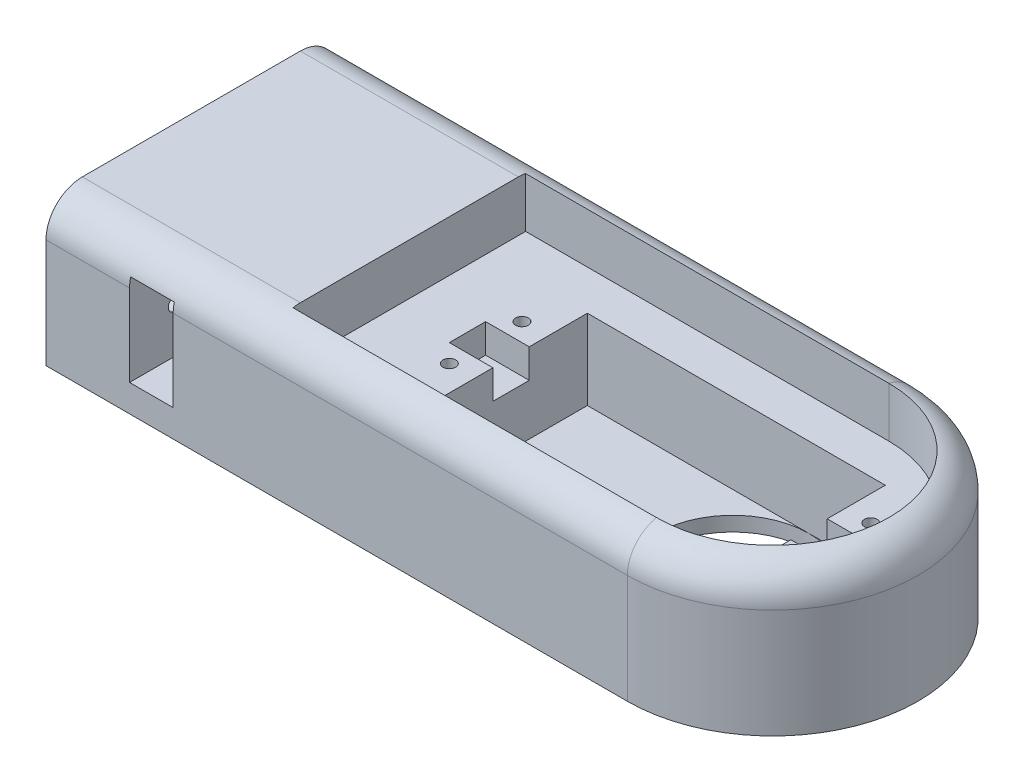
SolidWorks part; units mm, degrees
ref_plane "Front Plane" through (0, 0, 0) normal (0, 0, 1) x (1, 0, 0)
ref_plane "Top Plane" through (0, 0, 0) normal (0, 1, 0) x (1, 0, 0)
ref_plane "Right Plane" through (0, 0, 0) normal (1, 0, 0) x (0, 0, -1)
sketch "Sketch1" plane through (0, 0, 0) normal (0, 1, 0) x (1, 0, 0)
  line L0 (0, 40) -> (0, 0)
  line L1 (0, 0) -> (80, 0)
  line L3 (80, 40) -> (0, 40)
  arc A0 (80, 0) -> (80, 40) centre (80, 20) ccw
  dimension "D1" = 40
  dimension "D2" = 80
extrude "Boss-Extrude1" add sketch "Sketch1" along normal blind 20 contours L1 A0 L3 L0
sketch "Sketch2" plane through (0, 20, 0) normal (0, 1, 0) x (1, 0, 0)
  line L0 (80, 40) -> (80, 0) construction
  line L1 (80, 40) -> (0, 40) construction
  line L2 (85, 30.5) -> (44, 30.5)
  line L3 (85, 30.5) -> (85, 9.5)
  line L4 (85, 9.5) -> (44, 9.5)
  line L5 (44, 30.5) -> (44, 9.5)
  line L6 (85, 30.5) -> (44, 9.5) construction
  line L7 (85, 9.5) -> (44, 30.5) construction
  line L8 (88.5, 25) -> (40.5, 25)
  line L9 (88.5, 25) -> (88.5, 15)
  line L10 (88.5, 15) -> (40.5, 15)
  line L11 (40.5, 25) -> (40.5, 15)
  line L12 (88.5, 25) -> (40.5, 15) construction
  line L13 (88.5, 15) -> (40.5, 25) construction
  line L16 (30, 40) -> (30, 0)
  line L17 (30, 36) -> (30, 4)
  line L20 (0, 4) -> (80, 4)
  line L21 (80, 36) -> (0, 36)
  line L22 (30, 4) -> (80, 4)
  line L23 (80, 36) -> (30, 36)
  arc A0 (80, 0) -> (80, 40) centre (80, 20) ccw construction
  circle A1 centre (40.5, 25) radius 0.875
  circle A2 centre (40.5, 15) radius 0.875
  circle A3 centre (88.5, 25) radius 0.875
  circle A4 centre (88.5, 15) radius 0.875
  arc A8 (80, 4) -> (80, 36) centre (80, 20) ccw
  arc A9 (80, 4) -> (80, 36) centre (80, 20) ccw
  point P4 (64.5, 20)
  point P9 (64.5, 20)
  dimension "D7" = 1.75
  dimension "D1" = 5
  dimension "D2" = 21
  dimension "D3" = 41
  dimension "D4" = 10
  dimension "D5" = 48
  dimension "D6" = 20
  dimension "D8" = 4
  dimension "D9" = 30
extrude "Cut-Extrude2" cut sketch "Sketch2" against normal blind 7 contours L22 A9 L23 L17 A4 L10 L3 L4 L5 A2 L11 A1 L8 L2 A3 L9 | A2 L10 L5 L8 A1 L11 | A4 L9 A3 L8 L3 L10 region at (86.7009, 20, -20) region at (42.2991, 20, -20) region at (55, 20, -35.2665)
extrude "Cut-Extrude3" cut sketch "Sketch2<7>" against normal blind 18 contours L10 L3 L8 L5 | L3 L10 L5 L4 | L8 L3 L2 L5 region at (64.5, 20, -27.75) region at (64.5, 20, -20) region at (64.5, 20, -12.25)
sketch "Sketch2<7>" plane through (0, 20, 0) normal (0, 1, 0) x (1, 0, 0) same geometry as "Sketch2"
extrude "Cut-Extrude4" cut sketch "Sketch2<8>" against normal blind 16 contours A1 | A2 | A3 | A4
sketch "Sketch2<8>" plane through (0, 20, 0) normal (0, 1, 0) x (1, 0, 0) same geometry as "Sketch2"
sketch "Sketch5" plane through (0, 2, 0) normal (0, 1, 0) x (1, 0, 0)
  line L0 (85, 30.5) -> (44, 30.5) construction
  line L1 (85, 30.5) -> (85, 9.5) construction
  line L2 (85, 9.5) -> (44, 9.5) construction
  circle A0 centre (74.5, 20) radius 10.5
extrude "Cut-Extrude5" cut sketch "Sketch5" against normal blind 16
sketch "Sketch6" plane through (0, 0, 0) normal (-1, 0, 0) x (0, 0, 1)
  line L0 (-40, 20) -> (0, 0) construction
  line L2 (-8.5, 16.25) -> (-31.5, 16.25)
  line L3 (-8.5, 16.25) -> (-8.5, 3.75)
  line L4 (-8.5, 3.75) -> (-31.5, 3.75)
  line L5 (-31.5, 16.25) -> (-31.5, 3.75)
  line L6 (-8.5, 16.25) -> (-31.5, 3.75) construction
  line L7 (-8.5, 3.75) -> (-31.5, 16.25) construction
  circle A0 centre (-6.2, 10) radius 0.875
  circle A1 centre (-33.8, 10) radius 0.875
  point P5 (-20, 10)
  dimension "D3" = 1.75
  dimension "D1" = 12.5
  dimension "D2" = 23
  dimension "D4" = 13.8
  dimension "D5" = 13.8
extrude "Cut-Extrude6" cut sketch "Sketch6" against normal blind 17.5
fillet "Fillet1" radius 5 2 edges at (40, 20, -40) (40, 20, 0)
sketch "Sketch7" plane through (0, 13, 0) normal (0, 1, 0) x (1, 0, 0)
  line L0 (85, 20) -> (91, 20)
  line L1 (85, 30.5) -> (85, 9.5) construction
  line L2 (91, 20) -> (91, 17.5)
  line L3 (91, 17.5) -> (38, 17.5)
  line L4 (38, 17.5) -> (38, 22.5)
  line L5 (38, 22.5) -> (91, 22.5)
  line L6 (91, 22.5) -> (91, 20)
  line L7 (44, 30.5) -> (44, 9.5) construction
  line M2 (85, 30.5) -> (85, 9.5)
  line M4 (44, 9.5) -> (44, 30.5)
  dimension "D1" = 2.5
  dimension "D2" = 2.5
  dimension "D3" = 6
  dimension "D4" = 6
extrude "Cut-Extrude7" cut sketch "Sketch7" against normal blind 4 contours L5 L3 M4 M2 | L5 L4 L3 M4 | L3 L2 L0 M2 | L6 L5 L0 M2 region at (88, 13, -21.25) region at (64.5, 13, -20) region at (88, 13, -18.75) region at (41, 13, -20)
sketch "Sketch8" plane through (0, 0, -8.5) normal (0, 0, -1) x (-1, 0, 0)
  line L0 (-17.5, 3.75) -> (0, 3.75) construction
  line L1 (-17.5, 16.25) -> (0, 16.25) construction
  line L2 (-17.5, 3.75) -> (-17.5, 16.25) construction
  line L3 (-17.5, 3.75) -> (-11.5, 3.75)
  line L4 (-17.5, 16.25) -> (-11.5, 16.25)
  line L5 (-17.5, 3.75) -> (-17.5, 16.25)
  line L6 (-11.5, 3.75) -> (-11.5, 16.25)
  dimension "D1" = 6
extrude "Cut-Extrude8" cut sketch "Sketch8" against normal through all both and the other way through all
